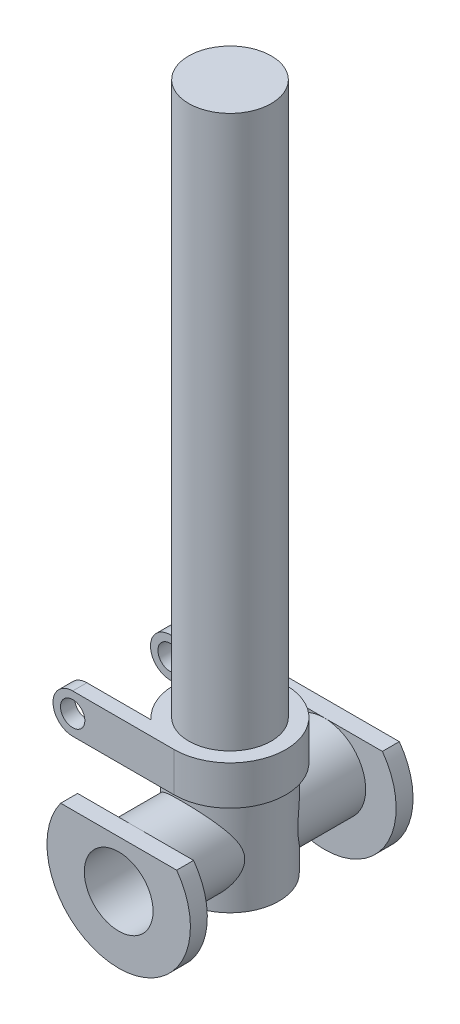
SolidWorks part; units mm, degrees
ref_plane "Front Plane" through (0, 0, 0) normal (0, 0, 1) x (1, 0, 0)
ref_plane "Top Plane" through (0, 0, 0) normal (0, 1, 0) x (1, 0, 0)
ref_plane "Right Plane" through (0, 0, 0) normal (1, 0, 0) x (0, 0, -1)
sketch "Sketch1" plane through (0, 0, 0) normal (0, 1, 0) x (1, 0, 0)
  circle A0 centre (0, 0) radius 61
  dimension "D1" = 122
extrude "Boss-Extrude1" add sketch "Sketch1" along normal blind 815.9823
sketch "Sketch2" plane through (0, 0, 0) normal (0, -1, 0) x (-1, 0, 0)
  line L0 (0, 82.5) -> (179, 82.5)
  line L1 (179, 82.5) -> (179, 61.5)
  line L2 (179, 61.5) -> (54.9909, 61.5)
  line L4 (179, -82.5) -> (179, -61.5)
  line L5 (0, -82.5) -> (179, -82.5)
  line L6 (179, -61.5) -> (54.9909, -61.5)
  arc A0 (0, 82.5) -> (0, -82.5) centre (0, 0) ccw
  arc A1 (54.9909, -61.5) -> (54.9909, 61.5) centre (0, 0) ccw
  dimension "D1" = 165
  dimension "D2" = 179
  dimension "D3" = 21
extrude "Boss-Extrude2" add sketch "Sketch2" along normal blind 58
sketch "Sketch3" plane through (0, 0, -82.5) normal (0, 0, -1) x (-1, 0, 0)
  line L0 (0, -29) -> (150, -29)
  line L1 (0, -58) -> (0, 0) construction
  circle A0 centre (150, -29) radius 29
  circle A1 centre (150, -29) radius 18
  line M1 (179, 0) -> (0, 0)
  line M3 (0, -58) -> (179, -58)
  line M4 (179, -58) -> (179, 0)
  dimension "D2" = 58
  dimension "D3" = 36
  dimension "D1" = 150
extrude "Cut-Extrude1" cut sketch "Sketch3" against normal blind 493 contours A0 M4 M1 | A0 M3 M4 region at (-172.5223, -6.4777, -82.5) region at (-172.5223, -51.5223, -82.5)
extrude "Cut-Extrude2" cut sketch "Sketch3<3>" against normal blind 493 contours A1 region at (-150, -11.5091, -82.5)
sketch "Sketch3<3>" plane through (0, 0, -82.5) normal (0, 0, -1) x (-1, 0, 0) same geometry as "Sketch3"
sketch "Sketch6" plane through (0, 0, 0) normal (0, 0, 1) x (1, 0, 0)
  line L0 (0, -58) -> (0, -61)
  line L2 (72.5, -61) -> (-72.5, -61)
  line L3 (72.5, -61) -> (72.5, -202)
  line L4 (72.5, -202) -> (-72.5, -202)
  line L5 (-72.5, -61) -> (-72.5, -202)
  circle A0 centre (0, -131.5) radius 61
  circle A1 centre (0, -131.5) radius 106
  point P8 (0, -61)
  dimension "D4" = 122
  dimension "D5" = 212
  dimension "D6" = 212
  dimension "D1" = 3
  dimension "D2" = 141
  dimension "D3" = 145
extrude "Boss-Extrude3" add sketch "Sketch6" along normal blind 139.5 and the other way blind 139.5 separate body contours A0
sketch "Sketch7" plane through (0, 0, -139.5) normal (0, 0, -1) x (-1, 0, 0)
  circle A0 centre (0, -132.8863) radius 106
  dimension "D1" = 212
extrude "Boss-Extrude5" add sketch "Sketch7" along normal blind 25
sketch "Sketch8" plane through (0, 0, -139.5) normal (0, 0, 1) x (1, 0, 0)
  line L0 (0, -70.5) -> (144.5908, -70.5)
  line L1 (144.5908, -70.5) -> (144.5908, 11.0252)
  line L2 (144.5908, 11.0252) -> (-136.3144, 11.0252)
  line L3 (-136.3144, 11.0252) -> (-136.3144, -70.5)
  line L4 (-136.3144, -70.5) -> (0, -70.5)
  circle A0 centre (0, -131.5) radius 61 construction
  circle A1 centre (0, -131.5) radius 61 construction
extrude "Cut-Extrude3" cut sketch "Sketch8" against normal blind 51
mirror "Mirror1" about plane through (0, 0, 0) normal (0, 0, 1) of "Boss-Extrude5", "Cut-Extrude3"
sketch "Sketch9" plane through (0, -58, 0) normal (0, -1, 0) x (1, 0, 0)
  circle A0 centre (0, 0) radius 72.5
  dimension "D1" = 145
extrude "Boss-Extrude6" add sketch "Sketch9" along normal blind 141 contours A0
sketch "Sketch11" plane through (0, 0, -164.5) normal (0, 0, -1) x (-1, 0, 0)
  circle A0 centre (0, -141.7396) radius 38.5
  dimension "D1" = 77
extrude "Cut-Extrude6" cut sketch "Sketch11" against normal blind 450
sketch "Sketch12" plane through (0, 0, -164.5) normal (0, 0, -1) x (-1, 0, 0)
  circle A0 centre (0, -140.5865) radius 50.8
  dimension "D1" = 101.6
extrude "Cut-Extrude7" cut sketch "Sketch12" against normal blind 630
